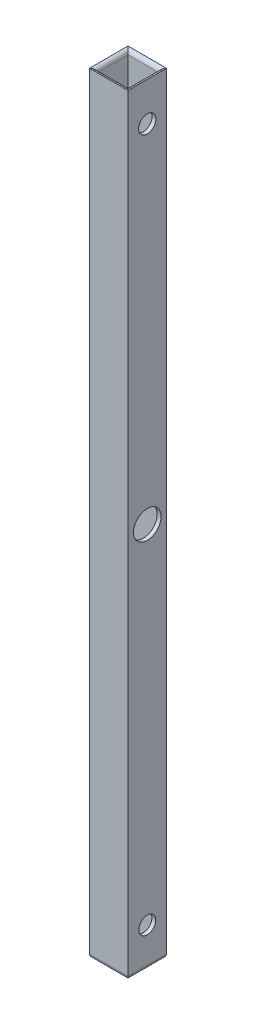
SolidWorks part; units mm, degrees
ref_plane "Front Plane" through (0, 0, 0) normal (0, 0, 1) x (1, 0, 0)
ref_plane "Top Plane" through (0, 0, 0) normal (0, 1, 0) x (1, 0, 0)
ref_plane "Right Plane" through (0, 0, 0) normal (1, 0, 0) x (0, 0, -1)
sketch "Sketch1" plane through (0, 0, 0) normal (0, 1, 0) x (1, 0, 0)
  line L1 (-5, 5) -> (5, 5)
  line L2 (-5, 5) -> (-5, -5)
  line L3 (-5, -5) -> (5, -5)
  line L4 (5, 5) -> (5, -5)
  line L5 (-5, 5) -> (5, -5) construction
  line L6 (-5, -5) -> (5, 5) construction
  point P0 (0, 0)
  dimension "D1" = 10
  dimension "D2" = 10
extrude "Boss-Extrude2" add sketch "Sketch1" along normal blind 200
sketch "Sketch3" plane through (0, 200, 0) normal (0, 1, 0) x (1, 0, 0)
  line L0 (0, 4) -> (0, 5)
  line L1 (-4, 4) -> (4, 4)
  line L2 (-4, 4) -> (-4, -4)
  line L3 (-4, -4) -> (4, -4)
  line L4 (4, 4) -> (4, -4)
  line L5 (-4, 4) -> (4, -4) construction
  line L6 (-4, -4) -> (4, 4) construction
  line L7 (5, 5) -> (-5, 5) construction
  line L8 (4, 0) -> (5, 0)
  line L9 (5, -5) -> (5, 5) construction
  line L10 (-4, 0) -> (-5, 0)
  line L11 (-5, 5) -> (-5, -5) construction
  line L12 (0, -4) -> (0, -5)
  line L13 (-5, -5) -> (5, -5) construction
  point P0 (0, 0)
  dimension "D1" = 1
  dimension "D2" = 1
extrude "Cut-Extrude1" cut sketch "Sketch3" against normal blind 200 contours L4 L1 L2 L3 region at (0, 200, 0)
sketch "Sketch4" plane through (5, 0, 0) normal (1, 0, 0) x (0, 0, -1)
  line L0 (-5, 0) -> (5, 0) construction
  line L4 (5, 200) -> (5, 0) construction
  line L5 (-5, 200) -> (-5, 0) construction
  circle A0 centre (0, 100) radius 3.575
  circle A1 centre (0, 190) radius 2.25
  circle A2 centre (0, 10) radius 2.2
  dimension "D2" = 7.15
  dimension "D3" = 4.5
  dimension "D1" = 4.4
  dimension "D4" = 10
  dimension "D5" = 5
  dimension "D6" = 100
  dimension "D7" = 5
  dimension "D8" = 5
  dimension "D9" = 190
extrude "Cut-Extrude2" cut sketch "Sketch4" against normal through all
fillet "Fillet1" radius 1 8 edges at (4, 200, 0) (-4, 200, 0) (0, 200, 4) (0, 200, -4) (5, 0, 0) (0, 0, -5) (-5, 0, 0) (0, 0, 5)
